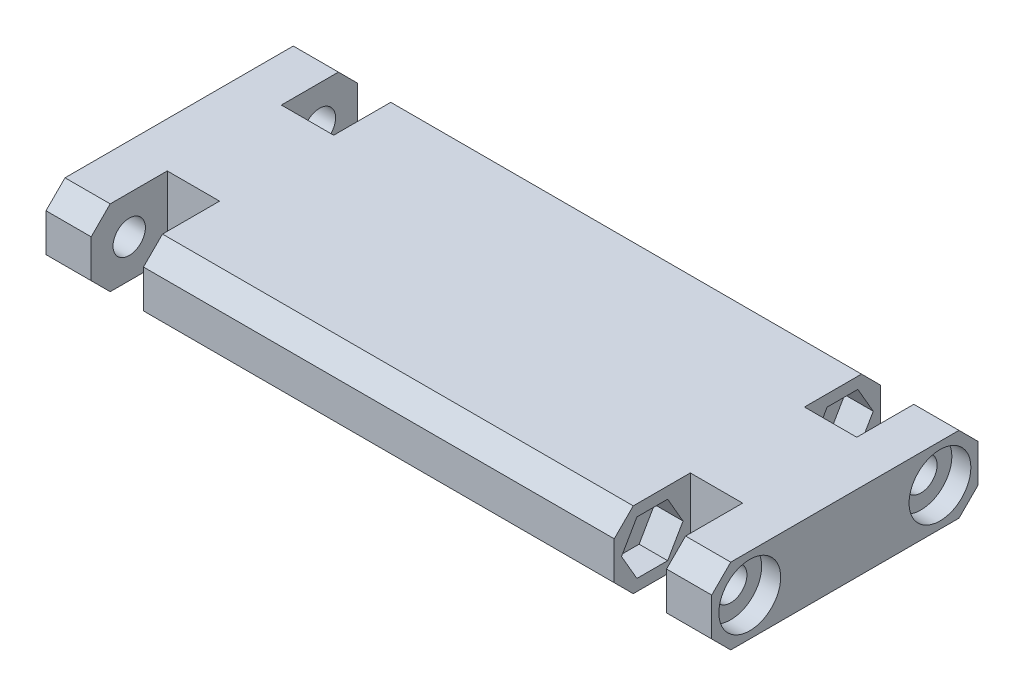
SolidWorks part; units mm, degrees
ref_plane "Front Plane" through (0, 0, 0) normal (0, 0, 1) x (1, 0, 0)
ref_plane "Top Plane" through (0, 0, 0) normal (0, 1, 0) x (1, 0, 0)
ref_plane "Right Plane" through (0, 0, 0) normal (1, 0, 0) x (0, 0, -1)
sketch "Sketch1" plane through (0, 0, 0) normal (0, 1, 0) x (1, 0, 0)
  line L1 (-35, -14) -> (35, -14)
  line L2 (-35, -14) -> (-35, 14)
  line L3 (-35, 14) -> (35, 14)
  line L4 (35, -14) -> (35, 14)
  line L5 (-35, -14) -> (35, 14) construction
  line L6 (-35, 14) -> (35, -14) construction
  point P0 (0, 0)
  dimension "D1" = 70
  dimension "D2" = 28
extrude "Boss-Extrude1" add sketch "Sketch1" along normal blind 8
sketch "Sketch2" plane through (0, 8, 0) normal (0, 1, 0) x (1, 0, 0)
  line L0 (35, 14) -> (-35, 14) construction
  line L1 (-30.25, 14) -> (-24.75, 14)
  line L2 (-30.25, 14) -> (-30.25, 6)
  line L3 (-30.25, 6) -> (-24.75, 6)
  line L4 (-24.75, 14) -> (-24.75, 6)
  line L5 (0, 0) -> (0, 14) construction
  line L6 (24.75, 14) -> (24.75, 6)
  line L7 (30.25, 6) -> (24.75, 6)
  line L8 (30.25, 14) -> (30.25, 6)
  line L9 (30.25, 14) -> (24.75, 14)
  dimension "D1" = 5.5
  dimension "D2" = 8
  dimension "D3" = 49.5
extrude "Cut-Extrude1" cut sketch "Sketch2" against normal through all
hole_wizard "CBORE for M3 Cheese Head Screw1" positions "Sketch7" profile "Sketch8" counterbore size "M3" standard "ISO" end condition up to next
sketch "Sketch7" plane through (35, 0, 0) normal (1, 0, 0) x (0, 0, -1)
  line L0 (-14, 8) -> (14, 8) construction
  line L1 (14, 8) -> (14, 0) construction
  point P0 (10, 4)
  dimension "D1" = 4
  dimension "D2" = 4
sketch "Sketch8" plane through (35, 4, -10) normal (0, 1, 0) x (0, 0, -1)
  line L0 (0, 0) -> (0, 56.75)
  line L1 (0, 56.75) -> (1.7, 56.75)
  line L3 (1.7, 56.75) -> (1.7, 2)
  line L4 (1.7, 2) -> (3.25, 2)
  line L5 (3.25, 2) -> (3.25, 0)
  line L7 (3.25, 0) -> (0, 0)
  line L11 (0, -6.35) -> (0, 107.95) construction
  dimension "Thru Hole Dia." = 3.4
  dimension "Thru Hole Depth" = 56.75
  dimension "C'Bore Dia." = 6.5
  dimension "C'Bore Depth" = 2
sketch "Sketch9" plane through (24.75, 0, 0) normal (1, 0, 0) x (0, 0, -1)
  line L1 (11.6166, 6.8) -> (8.3834, 6.8)
  line L2 (8.3834, 6.8) -> (6.7668, 4)
  line L3 (6.7668, 4) -> (8.3834, 1.2)
  line L4 (8.3834, 1.2) -> (11.6166, 1.2)
  line L5 (11.6166, 1.2) -> (13.2332, 4)
  line L6 (13.2332, 4) -> (11.6166, 6.8)
  circle A0 centre (10, 4) radius 2.8 construction
  dimension "D1" = 5.6
extrude "Cut-Extrude2" cut sketch "Sketch9" against normal blind 3
mirror "Mirror1" about plane through (0, 0, 0) normal (1, 0, 0) of "Cut-Extrude2", "CBORE for M3 Cheese Head Screw1"
mirror "Mirror2" about plane through (0, 0, 0) normal (0, 0, 1) of "Cut-Extrude1", "CBORE for M3 Cheese Head Screw1", "Cut-Extrude2", "Mirror1"
chamfer "Chamfer1" distance 2 angle 45 12 edges at (32.625, 0, -14) (32.625, 8, -14) (0, 0, -14) (0, 8, -14) (-32.625, 0, -14) (-32.625, 8, -14) (-32.625, 0, 14) (32.625, 0, 14) (0, 0, 14) (32.625, 8, 14) (-32.625, 8, 14) (0, 8, 14)
